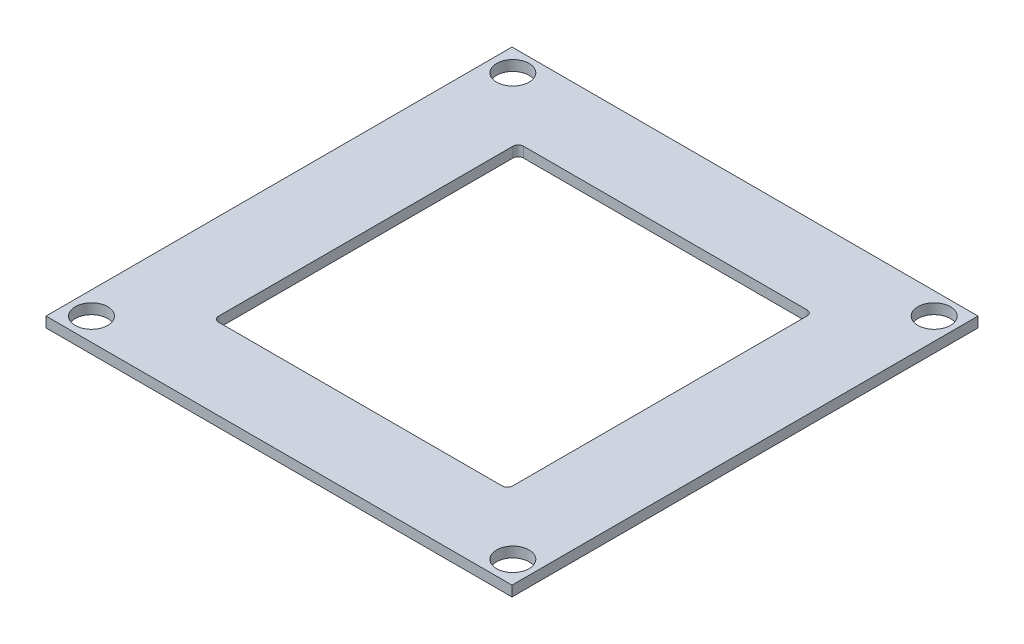
SolidWorks part; units mm, degrees
material "Acrylic (Medium-high impact)"
ref_plane "Front" through (0, 0, 0) normal (0, 0, 1) x (1, 0, 0)
ref_plane "Top" through (0, 0, 0) normal (0, 1, 0) x (1, 0, 0)
ref_plane "Right" through (0, 0, 0) normal (1, 0, 0) x (0, 0, -1)
sketch "Sketch1" plane through (0, 0, 0) normal (0, 1, 0) x (1, 0, 0)
  line L1 (0, -143.396) -> (286.792, -143.396)
  line L2 (0, -143.396) -> (0, 143.396)
  line L3 (0, 143.396) -> (286.792, 143.396)
  line L4 (286.792, -143.396) -> (286.792, 143.396)
  point P6 (0, 0)
  dimension "D1" = 286.792
  dimension "D2" = 286.792
extrude "Boss-Extrude1" add sketch "Sketch1" along normal blind 6.35
other "PropertyManager"
sketch "Sketch2" plane through (0, 0, 0) normal (0, -1, 0) x (1, 0, 0)
  line L0 (230.9625, -90.9002) -> (56.3375, 90.3922) construction
  line L2 (234.14, 93.5697) -> (53.16, 93.5697)
  line L3 (234.14, 93.5697) -> (234.14, -94.0777)
  line L4 (234.14, -94.0777) -> (53.16, -94.0777)
  line L5 (53.16, 93.5697) -> (53.16, -94.0777)
  line L6 (234.14, 93.5697) -> (53.16, -94.0777) construction
  line L7 (234.14, -94.0777) -> (53.16, 93.5697) construction
  circle A0 centre (273.3, -129.904) radius 10
  circle A1 centre (14, -129.904) radius 10
  circle A2 centre (14, 129.396) radius 10
  circle A3 centre (273.3, 129.396) radius 10
  arc A4 (53.1625, -92.9527) -> (54.285, -94.0753) centre (53.7213, -93.5165) ccw construction
  point P16 (143.65, -0.254)
extrude "Cut-Extrude1" cut sketch "Sketch2" against normal blind 6.35
fillet "Fillet1" radius 3.175 4 edges at (53.16, 3.175, -94.0777) (234.14, 3.175, -94.0777) (234.14, 3.175, 93.5697) (53.16, 3.175, 93.5697)
equation "\"thick\"= .25in"
equation "\"tol\"= .01"
equation "\"ftprnt\"= 30cm"
equation "\"D1@Sketch1\"    = \"ftprnt\"-(\"thick\"*2)-(\"tol\"*2)"
equation "\"D1@Boss-Extrude1\"=\"thick\""
equation "\"height\"= 5cm"
equation "\"D2@Sketch1\"    = \"ftprnt\"-(\"thick\"*2)-(\"tol\"*2)"
